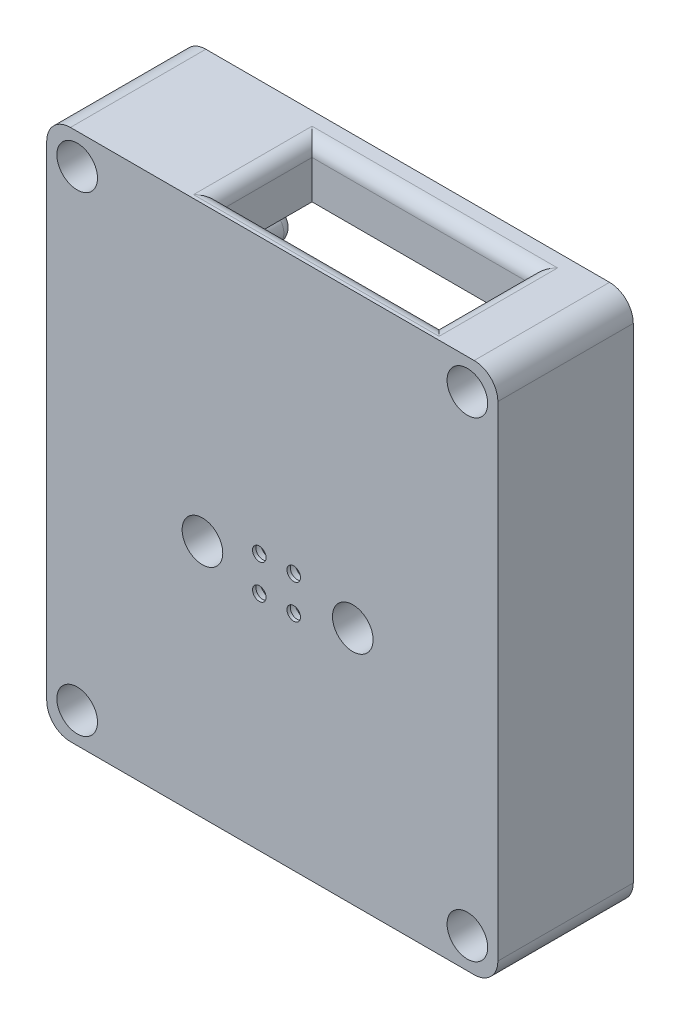
SolidWorks part; units mm, degrees
material "ABS"
ref_plane "Front Plane" through (0, 0, 0) normal (0, 0, 1) x (1, 0, 0)
ref_plane "Top Plane" through (0, 0, 0) normal (0, 1, 0) x (1, 0, 0)
ref_plane "Right Plane" through (0, 0, 0) normal (1, 0, 0) x (0, 0, -1)
sketch "Sketch1" plane through (0, 0, 0) normal (0, 0, 1) x (1, 0, 0)
  line L0 (12.065, 30.099) -> (12.065, 34.69) construction
  line L1 (0, 0) -> (24.13, 0) construction
  line L2 (0, 0) -> (0, 30.099) construction
  line L3 (0, 30.099) -> (24.13, 30.099) construction
  line L4 (24.13, 0) -> (24.13, 30.099) construction
  line L5 (-4.591, -4.591) -> (28.721, -4.591)
  line L6 (-4.591, -4.591) -> (-4.591, 34.69)
  line L7 (-4.591, 34.69) -> (28.721, 34.69)
  line L8 (28.721, -4.591) -> (28.721, 34.69)
  line L9 (12.065, -4.591) -> (12.065, 0) construction
  line L10 (-4.591, 15.0495) -> (0, 15.0495) construction
  line L11 (28.721, 15.0495) -> (24.13, 15.0495) construction
  line L12 (0, 0) -> (-4.591, 0) construction
  line L13 (0, 0) -> (0, -4.591) construction
  line L14 (-4.591, -4.591) -> (-3.4017, -3.4017) construction
  line L15 (-0.75, 15.0495) -> (0, 15.0495) construction
  line L16 (-1.2803, -1.2803) -> (-3.4017, -3.4017) construction
  line L17 (-3.841, -2.341) -> (-4.591, -2.341) construction
  line L18 (-0.75, -0.75) -> (24.88, -0.75)
  line L19 (-0.75, -0.75) -> (-0.75, 30.849)
  line L20 (-0.75, 30.849) -> (24.88, 30.849)
  line L21 (24.88, -0.75) -> (24.88, 30.849)
  line L22 (24.88, 15.0495) -> (24.13, 15.0495) construction
  line L23 (12.065, 30.849) -> (12.065, 30.099) construction
  line L24 (12.065, -0.75) -> (12.065, 0) construction
  line L25 (-1.2803, -1.2803) -> (-0.75, -0.75)
  line L26 (13.6479, 14.3949) -> (11.1079, 11.8549) construction
  line L27 (11.1079, 11.8549) -> (13.6479, 11.8549) construction
  line L28 (11.1079, 11.8549) -> (11.1079, 14.3949) construction
  line L29 (11.1079, 14.3949) -> (13.6479, 14.3949) construction
  line L30 (13.6479, 11.8549) -> (13.6479, 14.3949) construction
  line L31 (11.1079, 14.3949) -> (13.6479, 11.8549) construction
  circle A0 centre (3.048, 2.921) radius 1.125
  circle A1 centre (21.336, 2.921) radius 1.125
  circle A2 centre (3.048, 27.051) radius 1.125
  circle A3 centre (6.908, 13.095) radius 1.5
  circle A4 centre (18.0081, 13.095) radius 1.5
  circle A5 centre (-2.341, -2.341) radius 1.5
  circle A6 centre (26.471, -2.341) radius 1.5
  circle A7 centre (-2.341, 32.44) radius 1.5
  circle A8 centre (26.471, 32.44) radius 1.5
  circle A9 centre (3.048, 2.921) radius 2
  circle A10 centre (6.908, 13.095) radius 2
  circle A11 centre (18.0081, 13.095) radius 2
  circle A12 centre (21.336, 2.921) radius 2
  circle A13 centre (3.048, 27.051) radius 2
  circle A14 centre (11.1079, 14.3949) radius 1
  circle A15 centre (13.6479, 14.3949) radius 1
  circle A16 centre (11.1079, 11.8549) radius 1
  circle A17 centre (13.6479, 11.8549) radius 1
  circle A18 centre (12.3779, 13.1249) radius 3.625 construction
  circle A19 centre (12.3779, 13.1249) radius 3.125
  arc A20 (8.804, 13.7315) -> (8.8109, 12.4792) centre (12.3779, 13.1249) cw
  dimension "D5" = 2.25
  dimension "D13" = 3
  dimension "D16" = 3
  dimension "D17" = 3
  dimension "D20" = 4
  dimension "D25" = 2
  dimension "D26" = 7.25
  dimension "D27" = 0.5
  dimension "D1" = 24.13
  dimension "D2" = 30.099
  dimension "D3" = 3.048
  dimension "D4" = 2.921
  dimension "D6" = 21.336
  dimension "D7" = 2.921
  dimension "D8" = 3.048
  dimension "D9" = 27.051
  dimension "D11" = 13.095
  dimension "D12" = 6.908
  dimension "D14" = 18.0081
  dimension "D15" = 13.095
  dimension "D18" = 0.75
  dimension "D19" = 0.75
  dimension "D21" = 11.1079
  dimension "D22" = 11.8549
  dimension "D23" = 13.6479
  dimension "D24" = 14.3949
extrude "Boss-Extrude1" add sketch "Sketch1" along normal blind 1.25 contours L18 L21 L20 L19 A17 A16 A15 A14 A13 A12 A11 A10 A9 | L5 L8 L7 L6 A8 A6 A5 L19 L20 L21 L18 A7 | A10 A3 | A11 A4 | A9 A0 | A12 A1 | A13 A2 | A10 A18 A19 | A19 A14 A15 A16 A17 | A0 | A1 | A2 region at (-4.0759, 15.0495, 0) region at (-0.3431, 15.0495, 0) region at (3.048, 2.921, 0) region at (21.336, 2.921, 0) region at (3.048, 27.051, 0) region at (1.1046, 2.921, 0) region at (8.8277, 12.7921, 0) region at (8.9827, 13.4339, 0) region at (16.0647, 13.095, 0) region at (19.3926, 2.921, 0) region at (1.1046, 27.051, 0) region at (12.3779, 13.1249, 0)
extrude "Boss-Extrude3" add sketch "Sketch1<13>" against normal blind 4.5 contours A13 A2 | A10 A3 | A11 A4 | A12 A1 | A9 A0 | A0 | A1 | A2 region at (3.048, 2.921, 0) region at (21.336, 2.921, 0) region at (3.048, 27.051, 0) region at (1.1046, 2.921, 0) region at (8.8277, 12.7921, 0) region at (16.0647, 13.095, 0) region at (19.3926, 2.921, 0) region at (1.1046, 27.051, 0)
sketch "Sketch1<13>" plane through (0, 0, 0) normal (0, 0, 1) x (1, 0, 0) same geometry as "Sketch1"
extrude "Boss-Extrude4" add sketch "Sketch1<14>" against normal blind 8.75 contours L5 L8 L7 L6 A8 A6 A5 L19 L20 L21 L18 A7 region at (-4.0759, 15.0495, 0)
sketch "Sketch1<14>" plane through (0, 0, 0) normal (0, 0, 1) x (1, 0, 0) same geometry as "Sketch1"
chamfer "Chamfer1" distance 3 angle 15 5 edges at (5.048, 2.921, 0) (23.336, 2.921, 0) (5.048, 27.051, 0) (20.0081, 13.095, 0) (8.908, 13.095, 0) first distance on face at (5.048, 2.921, -4.5) first distance on face at (23.336, 2.921, -4.5) first distance on face at (5.048, 27.051, -4.5) first distance on face at (20.0081, 13.095, -4.5) first distance on face at (8.908, 13.095, -4.5)
sketch "Sketch2" plane through (0, 30.849, 0) normal (0, -1, 0) x (1, 0, 0)
  line L0 (-0.75, 0) -> (24.88, 0) construction
  line L1 (23.13, 0) -> (7, 0)
  line L2 (23.13, 0) -> (23.13, -6.75)
  line L3 (23.13, -6.75) -> (7, -6.75)
  line L4 (7, 0) -> (7, -6.75)
  line L6 (-0.75, -8.75) -> (24.88, -8.75) construction
  line L7 (-0.75, -8.75) -> (-0.75, 0) construction
  line L8 (24.88, -8.75) -> (24.88, 0) construction
  dimension "D1" = 0
  dimension "D2" = 1.75
  dimension "D3" = 2
  dimension "D4" = 7.75
extrude "Cut-Extrude1" cut sketch "Sketch2" against normal up to surface (3.841 mm away) up to face at (12.065, 34.69, -3.75)
extrude "Boss-Extrude6" add sketch "Sketch1<17>" against normal blind 1.25 contours A10 A18 A19 | A19 A17 A16 A15 A14 region at (8.9827, 13.4339, 0) region at (12.3779, 13.1249, 0)
sketch "Sketch1<17>" plane through (0, 0, 0) normal (0, 0, 1) x (1, 0, 0) same geometry as "Sketch1"
fillet "Fillet1" radius 1.75 4 edges at (28.721, 34.69, -3.75) (-4.591, 34.69, -3.75) (28.721, -4.591, -3.75) (-4.591, -4.591, -3.75)
fillet "Fillet4" radius 1 5 edges at (3.125, 30.849, 0) (24.005, 30.849, 0) (-0.75, 15.0495, 0) (12.065, -0.75, 0) (24.88, 15.0495, 0)
fillet "Fillet5" radius 0.25 14 edges at (24.1112, 3.266, -0.0271) (23.1911, 0.8185, 0) (21.2796, 0.12, -0.0085) (2.9916, 0.12, -0.0085) (4.7741, 5.1306, 0) (1.0654, 29.0336, 0) (19.2335, 4.7761, 0) (12.4527, 16.7492, 0) (20.8119, 13.08, 0) (5.0306, 25.0684, 0) (4.1042, 13.0796, 0)
fillet "Fillet6" radius 1 4 edges at (23.13, 34.69, -3.375) (15.065, 34.69, -6.75) (7, 34.69, -3.375) (15.065, 34.69, 0)
extrude "Boss-Extrude7" add sketch "Sketch1<18>" against normal blind 8.25 contours A0 | A1 | A2 region at (3.048, 2.921, 0) region at (21.336, 2.921, 0) region at (3.048, 27.051, 0)
sketch "Sketch1<18>" plane through (0, 0, 0) normal (0, 0, 1) x (1, 0, 0) same geometry as "Sketch1"
fillet "Fillet7" radius 0.75 3 edges at (4.173, 27.051, -8.25) (22.461, 2.921, -8.25) (4.173, 2.921, -8.25)
sketch "Sketch3" plane through (0, 0, -1.25) normal (0, 0, 1) x (1, 0, 0)
  circle A0 centre (11.1079, 14.3949) radius 1
  circle A1 centre (11.1079, 11.8549) radius 1
  circle A2 centre (13.6479, 11.8549) radius 1
  circle A3 centre (13.6479, 14.3949) radius 1
  circle A4 centre (11.1079, 11.8549) radius 0.5
  circle A5 centre (11.1079, 14.3949) radius 0.5
  circle A6 centre (13.6479, 11.8549) radius 0.5
  circle A7 centre (13.6479, 14.3949) radius 0.5
  dimension "D1" = 1
  dimension "D2" = 2
ref_plane "Plane1" through (0, 0, 0) normal (0, 0, -1) x (-1, 0, 0)
sketch "Sketch4" plane through (0, 0, 0) normal (0, 0, 1) x (1, 0, 0)
  circle A0 centre (11.1079, 14.3949) radius 1
  circle A1 centre (11.1079, 11.8549) radius 1
  circle A2 centre (13.6479, 11.8549) radius 1
  circle A3 centre (13.6479, 14.3949) radius 1
  circle A4 centre (11.1079, 11.8549) radius 0.5
  circle A5 centre (11.1079, 14.3949) radius 0.5
  circle A6 centre (13.6479, 11.8549) radius 0.5
  circle A7 centre (13.6479, 14.3949) radius 0.5
  dimension "D1" = 1
  dimension "D2" = 2
sketch "Sketch6" plane through (0, 0, 1.25) normal (0, 0, -1) x (-1, 0, 0)
  circle A0 centre (-13.6479, 14.3949) radius 1
  circle A1 centre (-13.6479, 11.8549) radius 1
  circle A2 centre (-11.1079, 11.8549) radius 1
  circle A3 centre (-11.1079, 14.3949) radius 1
  circle A4 centre (-13.6479, 11.8549) radius 0.5
  circle A5 centre (-13.6479, 14.3949) radius 0.5
  circle A6 centre (-11.1079, 11.8549) radius 0.5
  circle A7 centre (-11.1079, 14.3949) radius 0.5
  dimension "D1" = 1
  dimension "D2" = 2
extrude "Boss-Extrude8" add sketch "Sketch6" along normal blind 0.25
extrude "Boss-Extrude9" add sketch "Sketch4" along normal blind 0.25
extrude "Boss-Extrude10" add sketch "Sketch3" along normal blind 0.25
